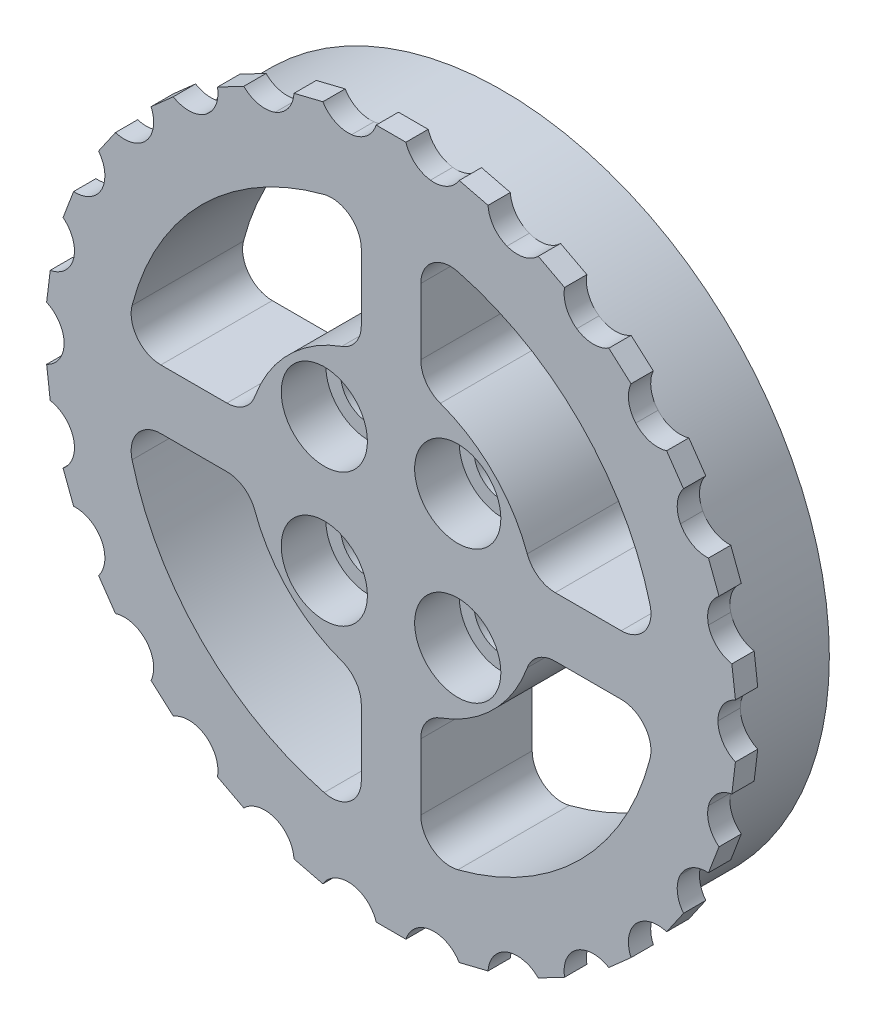
SolidWorks part; units mm, degrees
ref_plane "Front Plane" through (0, 0, 0) normal (0, 0, 1) x (1, 0, 0)
ref_plane "Top Plane" through (0, 0, 0) normal (0, 1, 0) x (1, 0, 0)
ref_plane "Right Plane" through (0, 0, 0) normal (1, 0, 0) x (0, 0, -1)
sketch "Sketch1" plane through (0, 0, 0) normal (0, 0, 1) x (1, 0, 0)
  line L0 (11.0482, 2) -> (15.4919, 2) construction
  line L1 (2, 15.4919) -> (2, 11.0482) construction
  line L2 (-15.4919, 2) -> (-11.0482, 2) construction
  line L3 (-2, 15.4919) -> (-2, 11.0482) construction
  line L4 (11.0482, 2) -> (15.4919, 2)
  line L5 (2, 15.4919) -> (2, 11.0482)
  line L6 (-15.4919, 2) -> (-11.0482, 2)
  line L7 (-2, 15.4919) -> (-2, 11.0482)
  line L8 (2, -11.0482) -> (2, -15.4919) construction
  line L9 (11.0482, -2) -> (15.4919, -2) construction
  line L10 (2, -11.0482) -> (2, -15.4919)
  line L11 (11.0482, -2) -> (15.4919, -2)
  line L12 (-15.4919, -2) -> (-11.0482, -2) construction
  line L13 (-2, -11.0482) -> (-2, -15.4919) construction
  line L14 (-15.4919, -2) -> (-11.0482, -2)
  line L15 (-2, -11.0482) -> (-2, -15.4919)
  circle A0 centre (0, 0) radius 22 construction
  circle A1 centre (0, 0) radius 22
  arc A2 (2, 11.0482) -> (3.3191, 9.1676) centre (4, 11.0482) ccw construction
  arc A3 (9.1676, 3.3191) -> (3.3191, 9.1676) centre (0, 0) ccw construction
  arc A4 (9.1676, 3.3191) -> (11.0482, 2) centre (11.0482, 4) ccw construction
  arc A5 (15.4919, 2) -> (17.4284, 4.5) centre (15.4919, 4) ccw construction
  arc A6 (17.4284, 4.5) -> (4.5, 17.4284) centre (0, 0) ccw construction
  arc A7 (4.5, 17.4284) -> (2, 15.4919) centre (4, 15.4919) ccw construction
  arc A8 (-17.4284, 4.5) -> (-15.4919, 2) centre (-15.4919, 4) ccw construction
  arc A9 (-11.0482, 2) -> (-9.1676, 3.3191) centre (-11.0482, 4) ccw construction
  arc A10 (-3.3191, 9.1676) -> (-9.1676, 3.3191) centre (0, 0) ccw construction
  arc A11 (-3.3191, 9.1676) -> (-2, 11.0482) centre (-4, 11.0482) ccw construction
  arc A12 (-2, 15.4919) -> (-4.5, 17.4284) centre (-4, 15.4919) ccw construction
  arc A13 (-4.5, 17.4284) -> (-17.4284, 4.5) centre (0, 0) ccw construction
  arc A14 (2, 11.0482) -> (3.3191, 9.1676) centre (4, 11.0482) ccw
  arc A15 (9.1676, 3.3191) -> (3.3191, 9.1676) centre (0, 0) ccw
  arc A16 (9.1676, 3.3191) -> (11.0482, 2) centre (11.0482, 4) ccw
  arc A17 (15.4919, 2) -> (17.4284, 4.5) centre (15.4919, 4) ccw
  arc A18 (17.4284, 4.5) -> (4.5, 17.4284) centre (0, 0) ccw
  arc A19 (4.5, 17.4284) -> (2, 15.4919) centre (4, 15.4919) ccw
  arc A20 (-17.4284, 4.5) -> (-15.4919, 2) centre (-15.4919, 4) ccw
  arc A21 (-11.0482, 2) -> (-9.1676, 3.3191) centre (-11.0482, 4) ccw
  arc A22 (-3.3191, 9.1676) -> (-9.1676, 3.3191) centre (0, 0) ccw
  arc A23 (-3.3191, 9.1676) -> (-2, 11.0482) centre (-4, 11.0482) ccw
  arc A24 (-2, 15.4919) -> (-4.5, 17.4284) centre (-4, 15.4919) ccw
  arc A25 (-4.5, 17.4284) -> (-17.4284, 4.5) centre (0, 0) ccw
  arc A26 (2, -15.4919) -> (4.5, -17.4284) centre (4, -15.4919) ccw construction
  arc A27 (3.3191, -9.1676) -> (2, -11.0482) centre (4, -11.0482) ccw construction
  arc A28 (3.3191, -9.1676) -> (9.1676, -3.3191) centre (0, 0) ccw construction
  arc A29 (11.0482, -2) -> (9.1676, -3.3191) centre (11.0482, -4) ccw construction
  arc A30 (17.4284, -4.5) -> (15.4919, -2) centre (15.4919, -4) ccw construction
  arc A31 (4.5, -17.4284) -> (17.4284, -4.5) centre (0, 0) ccw construction
  arc A32 (2, -15.4919) -> (4.5, -17.4284) centre (4, -15.4919) ccw
  arc A33 (3.3191, -9.1676) -> (2, -11.0482) centre (4, -11.0482) ccw
  arc A34 (3.3191, -9.1676) -> (9.1676, -3.3191) centre (0, 0) ccw
  arc A35 (11.0482, -2) -> (9.1676, -3.3191) centre (11.0482, -4) ccw
  arc A36 (17.4284, -4.5) -> (15.4919, -2) centre (15.4919, -4) ccw
  arc A37 (4.5, -17.4284) -> (17.4284, -4.5) centre (0, 0) ccw
  arc A38 (-4.5, -17.4284) -> (-2, -15.4919) centre (-4, -15.4919) ccw construction
  arc A39 (-17.4284, -4.5) -> (-4.5, -17.4284) centre (0, 0) ccw construction
  arc A40 (-15.4919, -2) -> (-17.4284, -4.5) centre (-15.4919, -4) ccw construction
  arc A41 (-9.1676, -3.3191) -> (-11.0482, -2) centre (-11.0482, -4) ccw construction
  arc A42 (-9.1676, -3.3191) -> (-3.3191, -9.1676) centre (0, 0) ccw construction
  arc A43 (-2, -11.0482) -> (-3.3191, -9.1676) centre (-4, -11.0482) ccw construction
  arc A44 (-4.5, -17.4284) -> (-2, -15.4919) centre (-4, -15.4919) ccw
  arc A45 (-17.4284, -4.5) -> (-4.5, -17.4284) centre (0, 0) ccw
  arc A46 (-15.4919, -2) -> (-17.4284, -4.5) centre (-15.4919, -4) ccw
  arc A47 (-9.1676, -3.3191) -> (-11.0482, -2) centre (-11.0482, -4) ccw
  arc A48 (-9.1676, -3.3191) -> (-3.3191, -9.1676) centre (0, 0) ccw
  arc A49 (-2, -11.0482) -> (-3.3191, -9.1676) centre (-4, -11.0482) ccw
extrude "Boss-Extrude1" add sketch "Sketch1" along normal blind 6
sketch "Sketch2" plane through (0, 0, 6) normal (0, 0, 1) x (1, 0, 0)
  line L0 (1, 23.2273) -> (-1, 23.2273) construction
  line L1 (6.5296, 22.313) -> (4.5877, 22.7916) construction
  line L2 (11.6797, 20.102) -> (9.9088, 21.0314) construction
  line L3 (16.151, 16.7227) -> (14.654, 18.049) construction
  line L4 (19.6837, 12.3716) -> (18.5476, 14.0176) construction
  line L5 (22.0725, 7.3015) -> (21.3633, 9.1715) construction
  line L6 (23.1784, 1.807) -> (22.9374, 3.7924) construction
  line L7 (22.9374, -3.7924) -> (23.1784, -1.807) construction
  line L8 (21.3633, -9.1715) -> (22.0725, -7.3015) construction
  line L9 (18.5476, -14.0176) -> (19.6837, -12.3716) construction
  line L10 (14.654, -18.049) -> (16.151, -16.7227) construction
  line L11 (9.9088, -21.0314) -> (11.6797, -20.102) construction
  line L12 (4.5877, -22.7916) -> (6.5296, -22.313) construction
  line L13 (-1, -23.2273) -> (1, -23.2273) construction
  line L14 (-6.5296, -22.313) -> (-4.5877, -22.7916) construction
  line L15 (-11.6797, -20.102) -> (-9.9088, -21.0314) construction
  line L16 (-16.151, -16.7227) -> (-14.654, -18.049) construction
  line L17 (-19.6837, -12.3716) -> (-18.5476, -14.0176) construction
  line L18 (-22.0725, -7.3015) -> (-21.3633, -9.1715) construction
  line L19 (-23.1784, -1.807) -> (-22.9374, -3.7924) construction
  line L20 (-22.9374, 3.7924) -> (-23.1784, 1.807) construction
  line L21 (-21.3633, 9.1715) -> (-22.0725, 7.3015) construction
  line L22 (-4.5877, 22.7916) -> (-6.5296, 22.313) construction
  line L23 (-9.9088, 21.0314) -> (-11.6797, 20.102) construction
  line L24 (-14.654, 18.049) -> (-16.151, 16.7227) construction
  line L25 (-18.5476, 14.0176) -> (-19.6837, 12.3716) construction
  line L26 (-4.5877, 22.7916) -> (-6.5296, 22.313)
  line L27 (-9.9088, 21.0314) -> (-11.6797, 20.102)
  line L28 (-14.654, 18.049) -> (-16.151, 16.7227)
  line L29 (-18.5476, 14.0176) -> (-19.6837, 12.3716)
  line L30 (-21.3633, 9.1715) -> (-22.0725, 7.3015)
  line L31 (-22.9374, 3.7924) -> (-23.1784, 1.807)
  line L32 (-23.1784, -1.807) -> (-22.9374, -3.7924)
  line L33 (-22.0725, -7.3015) -> (-21.3633, -9.1715)
  line L34 (-19.6837, -12.3716) -> (-18.5476, -14.0176)
  line L35 (-16.151, -16.7227) -> (-14.654, -18.049)
  line L36 (-11.6797, -20.102) -> (-9.9088, -21.0314)
  line L37 (-6.5296, -22.313) -> (-4.5877, -22.7916)
  line L38 (-1, -23.2273) -> (1, -23.2273)
  line L39 (4.5877, -22.7916) -> (6.5296, -22.313)
  line L40 (9.9088, -21.0314) -> (11.6797, -20.102)
  line L41 (14.654, -18.049) -> (16.151, -16.7227)
  line L42 (18.5476, -14.0176) -> (19.6837, -12.3716)
  line L43 (21.3633, -9.1715) -> (22.0725, -7.3015)
  line L44 (22.9374, -3.7924) -> (23.1784, -1.807)
  line L45 (23.1784, 1.807) -> (22.9374, 3.7924)
  line L46 (22.0725, 7.3015) -> (21.3633, 9.1715)
  line L47 (19.6837, 12.3716) -> (18.5476, 14.0176)
  line L48 (16.151, 16.7227) -> (14.654, 18.049)
  line L49 (11.6797, 20.102) -> (9.9088, 21.0314)
  line L50 (6.5296, 22.313) -> (4.5877, 22.7916)
  line L51 (1, 23.2273) -> (-1, 23.2273)
  line L54 (-2, 11.0482) -> (-2, 15.4919)
  line L55 (-15.4919, 2) -> (-11.0482, 2)
  line L56 (-2, 11.0482) -> (-2, 15.4919)
  line L57 (-15.4919, 2) -> (-11.0482, 2)
  line L58 (2, 15.4919) -> (2, 11.0482)
  line L59 (11.0482, 2) -> (15.4919, 2)
  line L60 (2, 15.4919) -> (2, 11.0482)
  line L61 (11.0482, 2) -> (15.4919, 2)
  line L62 (2, -11.0482) -> (2, -15.4919)
  line L63 (15.4919, -2) -> (11.0482, -2)
  line L64 (2, -11.0482) -> (2, -15.4919)
  line L65 (15.4919, -2) -> (11.0482, -2)
  line L66 (-11.0482, -2) -> (-15.4919, -2)
  line L67 (-2, -15.4919) -> (-2, -11.0482)
  line L68 (-11.0482, -2) -> (-15.4919, -2)
  line L69 (-2, -15.4919) -> (-2, -11.0482)
  arc A4 (-6.5296, -22.313) -> (-7.8013, -20.5704) centre (-8.5259, -22.4346) ccw construction
  arc A5 (-6.5296, -22.313) -> (-7.8013, -20.5704) centre (-8.5259, -22.4346) ccw
  arc A6 (-23.1784, -1.807) -> (-22.0001, 0) centre (-24, 0.0164) ccw construction
  arc A7 (-17.4284, 4.5) -> (-15.4919, 2) centre (-15.4919, 4) ccw
  arc A8 (-4.5, 17.4284) -> (-17.4284, 4.5) centre (0, 0) ccw
  arc A9 (-2, 15.4919) -> (-4.5, 17.4284) centre (-4, 15.4919) ccw
  arc A10 (-3.3191, 9.1676) -> (-2, 11.0482) centre (-4, 11.0482) ccw
  arc A11 (-3.3191, 9.1676) -> (-9.1676, 3.3191) centre (0, 0) ccw
  arc A12 (-11.0482, 2) -> (-9.1676, 3.3191) centre (-11.0482, 4) ccw
  arc A13 (-17.4284, 4.5) -> (-15.4919, 2) centre (-15.4919, 4) ccw
  arc A14 (-4.5, 17.4284) -> (-17.4284, 4.5) centre (0, 0) ccw
  arc A15 (-2, 15.4919) -> (-4.5, 17.4284) centre (-4, 15.4919) ccw
  arc A16 (-3.3191, 9.1676) -> (-2, 11.0482) centre (-4, 11.0482) ccw
  arc A17 (-3.3191, 9.1676) -> (-9.1676, 3.3191) centre (0, 0) ccw
  arc A18 (-11.0482, 2) -> (-9.1676, 3.3191) centre (-11.0482, 4) ccw
  arc A19 (-23.1784, -1.807) -> (-22.0001, 0) centre (-24, 0.0164) ccw
  arc A20 (9.1676, 3.3191) -> (3.3191, 9.1676) centre (0, 0) ccw
  arc A21 (2, 11.0482) -> (3.3191, 9.1676) centre (4, 11.0482) ccw
  arc A22 (4.5, 17.4284) -> (2, 15.4919) centre (4, 15.4919) ccw
  arc A23 (17.4284, 4.5) -> (4.5, 17.4284) centre (0, 0) ccw
  arc A24 (15.4919, 2) -> (17.4284, 4.5) centre (15.4919, 4) ccw
  arc A25 (9.1676, 3.3191) -> (11.0482, 2) centre (11.0482, 4) ccw
  arc A26 (9.1676, 3.3191) -> (3.3191, 9.1676) centre (0, 0) ccw
  arc A27 (2, 11.0482) -> (3.3191, 9.1676) centre (4, 11.0482) ccw
  arc A28 (4.5877, -22.7916) -> (2.6518, -21.8397) centre (2.8766, -23.827) ccw construction
  arc A29 (-4.5877, 22.7916) -> (-2.6518, 21.8397) centre (-2.8766, 23.827) ccw construction
  arc A30 (-2.6518, 21.8397) -> (-1, 23.2273) centre (-2.9092, 23.823) ccw construction
  arc A31 (7.8013, 20.5704) -> (9.9088, 21.0314) centre (8.4951, 22.4462) ccw construction
  arc A32 (1, 23.2273) -> (2.6518, 21.8397) centre (2.9092, 23.823) ccw construction
  arc A33 (2.6518, 21.8397) -> (4.5877, 22.7916) centre (2.8766, 23.827) ccw construction
  arc A34 (6.5296, 22.313) -> (7.8013, 20.5704) centre (8.5259, 22.4346) ccw construction
  arc A36 (11.6797, 20.102) -> (12.4975, 18.1057) centre (13.6471, 19.7423) ccw construction
  arc A37 (12.4975, 18.1057) -> (14.654, 18.049) centre (13.62, 19.761) ccw construction
  arc A38 (16.151, 16.7227) -> (16.4673, 14.5887) centre (17.9752, 15.9026) ccw construction
  arc A39 (16.4673, 14.5887) -> (18.5476, 14.0176) centre (17.9533, 15.9272) ccw construction
  arc A40 (19.6837, 12.3716) -> (19.4801, 10.2239) centre (21.2586, 11.1388) ccw construction
  arc A41 (19.4801, 10.2239) -> (21.3633, 9.1715) centre (21.2433, 11.1679) ccw construction
  arc A42 (22.0725, 7.3015) -> (21.3608, 5.265) centre (23.3065, 5.7276) ccw construction
  arc A43 (21.3608, 5.265) -> (22.9374, 3.7924) centre (23.2987, 5.7595) ccw construction
  arc A44 (23.1784, 1.807) -> (22.0001, 0) centre (24, -0.0164) ccw construction
  arc A45 (22.0001, 0) -> (23.1784, -1.807) centre (24, 0.0164) ccw construction
  arc A46 (22.9374, -3.7924) -> (21.3608, -5.265) centre (23.2987, -5.7595) ccw construction
  arc A47 (21.3608, -5.265) -> (22.0725, -7.3015) centre (23.3065, -5.7276) ccw construction
  arc A48 (21.3633, -9.1715) -> (19.4801, -10.2239) centre (21.2433, -11.1679) ccw construction
  arc A49 (19.4801, -10.2239) -> (19.6837, -12.3716) centre (21.2586, -11.1388) ccw construction
  arc A50 (18.5476, -14.0176) -> (16.4673, -14.5887) centre (17.9533, -15.9272) ccw construction
  arc A51 (16.4673, -14.5887) -> (16.151, -16.7227) centre (17.9752, -15.9026) ccw construction
  arc A52 (14.654, -18.049) -> (12.4975, -18.1057) centre (13.62, -19.761) ccw construction
  arc A53 (12.4975, -18.1057) -> (11.6797, -20.102) centre (13.6471, -19.7423) ccw construction
  arc A54 (9.9088, -21.0314) -> (7.8013, -20.5704) centre (8.4951, -22.4462) ccw construction
  arc A55 (7.8013, -20.5704) -> (6.5296, -22.313) centre (8.5259, -22.4346) ccw construction
  arc A56 (2.6518, -21.8397) -> (1, -23.2273) centre (2.9092, -23.823) ccw construction
  arc A57 (-1, -23.2273) -> (-2.6518, -21.8397) centre (-2.9092, -23.823) ccw construction
  arc A58 (-2.6518, -21.8397) -> (-4.5877, -22.7916) centre (-2.8766, -23.827) ccw construction
  arc A59 (-7.8013, -20.5704) -> (-9.9088, -21.0314) centre (-8.4951, -22.4462) ccw construction
  arc A60 (-11.6797, -20.102) -> (-12.4975, -18.1057) centre (-13.6471, -19.7423) ccw construction
  arc A61 (-12.4975, -18.1057) -> (-14.654, -18.049) centre (-13.62, -19.761) ccw construction
  arc A62 (-16.151, -16.7227) -> (-16.4673, -14.5887) centre (-17.9752, -15.9026) ccw construction
  arc A63 (-16.4673, -14.5887) -> (-18.5476, -14.0176) centre (-17.9533, -15.9272) ccw construction
  arc A64 (-19.6837, -12.3716) -> (-19.4801, -10.2239) centre (-21.2586, -11.1388) ccw construction
  arc A65 (-19.4801, -10.2239) -> (-21.3633, -9.1715) centre (-21.2433, -11.1679) ccw construction
  arc A66 (-22.0725, -7.3015) -> (-21.3608, -5.265) centre (-23.3065, -5.7276) ccw construction
  arc A67 (-21.3608, -5.265) -> (-22.9374, -3.7924) centre (-23.2987, -5.7595) ccw construction
  arc A68 (-21.3633, 9.1715) -> (-19.4801, 10.2239) centre (-21.2433, 11.1679) ccw construction
  arc A69 (-22.0001, 0) -> (-23.1784, 1.807) centre (-24, -0.0164) ccw construction
  arc A70 (-22.9374, 3.7924) -> (-21.3608, 5.265) centre (-23.2987, 5.7595) ccw construction
  arc A71 (-21.3608, 5.265) -> (-22.0725, 7.3015) centre (-23.3065, 5.7276) ccw construction
  arc A72 (-7.8013, 20.5704) -> (-6.5296, 22.313) centre (-8.5259, 22.4346) ccw construction
  arc A73 (-9.9088, 21.0314) -> (-7.8013, 20.5704) centre (-8.4951, 22.4462) ccw construction
  arc A74 (-12.4975, 18.1057) -> (-11.6797, 20.102) centre (-13.6471, 19.7423) ccw construction
  arc A75 (-14.654, 18.049) -> (-12.4975, 18.1057) centre (-13.62, 19.761) ccw construction
  arc A76 (-16.4673, 14.5887) -> (-16.151, 16.7227) centre (-17.9752, 15.9026) ccw construction
  arc A77 (-18.5476, 14.0176) -> (-16.4673, 14.5887) centre (-17.9533, 15.9272) ccw construction
  arc A78 (-19.4801, 10.2239) -> (-19.6837, 12.3716) centre (-21.2586, 11.1388) ccw construction
  arc A79 (-4.5877, 22.7916) -> (-2.6518, 21.8397) centre (-2.8766, 23.827) ccw
  arc A80 (-7.8013, 20.5704) -> (-6.5296, 22.313) centre (-8.5259, 22.4346) ccw
  arc A81 (-9.9088, 21.0314) -> (-7.8013, 20.5704) centre (-8.4951, 22.4462) ccw
  arc A82 (-12.4975, 18.1057) -> (-11.6797, 20.102) centre (-13.6471, 19.7423) ccw
  arc A83 (-14.654, 18.049) -> (-12.4975, 18.1057) centre (-13.62, 19.761) ccw
  arc A84 (-16.4673, 14.5887) -> (-16.151, 16.7227) centre (-17.9752, 15.9026) ccw
  arc A85 (-18.5476, 14.0176) -> (-16.4673, 14.5887) centre (-17.9533, 15.9272) ccw
  arc A86 (-19.4801, 10.2239) -> (-19.6837, 12.3716) centre (-21.2586, 11.1388) ccw
  arc A87 (-21.3633, 9.1715) -> (-19.4801, 10.2239) centre (-21.2433, 11.1679) ccw
  arc A88 (-21.3608, 5.265) -> (-22.0725, 7.3015) centre (-23.3065, 5.7276) ccw
  arc A89 (-22.9374, 3.7924) -> (-21.3608, 5.265) centre (-23.2987, 5.7595) ccw
  arc A90 (-22.0001, 0) -> (-23.1784, 1.807) centre (-24, -0.0164) ccw
  arc A91 (-21.3608, -5.265) -> (-22.9374, -3.7924) centre (-23.2987, -5.7595) ccw
  arc A92 (-22.0725, -7.3015) -> (-21.3608, -5.265) centre (-23.3065, -5.7276) ccw
  arc A93 (-19.4801, -10.2239) -> (-21.3633, -9.1715) centre (-21.2433, -11.1679) ccw
  arc A94 (-19.6837, -12.3716) -> (-19.4801, -10.2239) centre (-21.2586, -11.1388) ccw
  arc A95 (-16.4673, -14.5887) -> (-18.5476, -14.0176) centre (-17.9533, -15.9272) ccw
  arc A96 (-16.151, -16.7227) -> (-16.4673, -14.5887) centre (-17.9752, -15.9026) ccw
  arc A97 (-12.4975, -18.1057) -> (-14.654, -18.049) centre (-13.62, -19.761) ccw
  arc A98 (-11.6797, -20.102) -> (-12.4975, -18.1057) centre (-13.6471, -19.7423) ccw
  arc A99 (-7.8013, -20.5704) -> (-9.9088, -21.0314) centre (-8.4951, -22.4462) ccw
  arc A100 (-2.6518, -21.8397) -> (-4.5877, -22.7916) centre (-2.8766, -23.827) ccw
  arc A101 (-1, -23.2273) -> (-2.6518, -21.8397) centre (-2.9092, -23.823) ccw
  arc A102 (2.6518, -21.8397) -> (1, -23.2273) centre (2.9092, -23.823) ccw
  arc A103 (4.5877, -22.7916) -> (2.6518, -21.8397) centre (2.8766, -23.827) ccw
  arc A104 (7.8013, -20.5704) -> (6.5296, -22.313) centre (8.5259, -22.4346) ccw
  arc A105 (9.9088, -21.0314) -> (7.8013, -20.5704) centre (8.4951, -22.4462) ccw
  arc A106 (12.4975, -18.1057) -> (11.6797, -20.102) centre (13.6471, -19.7423) ccw
  arc A107 (14.654, -18.049) -> (12.4975, -18.1057) centre (13.62, -19.761) ccw
  arc A108 (16.4673, -14.5887) -> (16.151, -16.7227) centre (17.9752, -15.9026) ccw
  arc A109 (18.5476, -14.0176) -> (16.4673, -14.5887) centre (17.9533, -15.9272) ccw
  arc A110 (19.4801, -10.2239) -> (19.6837, -12.3716) centre (21.2586, -11.1388) ccw
  arc A111 (21.3633, -9.1715) -> (19.4801, -10.2239) centre (21.2433, -11.1679) ccw
  arc A112 (21.3608, -5.265) -> (22.0725, -7.3015) centre (23.3065, -5.7276) ccw
  arc A113 (22.9374, -3.7924) -> (21.3608, -5.265) centre (23.2987, -5.7595) ccw
  arc A114 (22.0001, 0) -> (23.1784, -1.807) centre (24, 0.0164) ccw
  arc A115 (23.1784, 1.807) -> (22.0001, 0) centre (24, -0.0164) ccw
  arc A116 (21.3608, 5.265) -> (22.9374, 3.7924) centre (23.2987, 5.7595) ccw
  arc A117 (22.0725, 7.3015) -> (21.3608, 5.265) centre (23.3065, 5.7276) ccw
  arc A118 (19.4801, 10.2239) -> (21.3633, 9.1715) centre (21.2433, 11.1679) ccw
  arc A119 (19.6837, 12.3716) -> (19.4801, 10.2239) centre (21.2586, 11.1388) ccw
  arc A120 (16.4673, 14.5887) -> (18.5476, 14.0176) centre (17.9533, 15.9272) ccw
  arc A121 (16.151, 16.7227) -> (16.4673, 14.5887) centre (17.9752, 15.9026) ccw
  arc A122 (12.4975, 18.1057) -> (14.654, 18.049) centre (13.62, 19.761) ccw
  arc A123 (11.6797, 20.102) -> (12.4975, 18.1057) centre (13.6471, 19.7423) ccw
  arc A124 (7.8013, 20.5704) -> (9.9088, 21.0314) centre (8.4951, 22.4462) ccw
  arc A125 (6.5296, 22.313) -> (7.8013, 20.5704) centre (8.5259, 22.4346) ccw
  arc A126 (2.6518, 21.8397) -> (4.5877, 22.7916) centre (2.8766, 23.827) ccw
  arc A127 (1, 23.2273) -> (2.6518, 21.8397) centre (2.9092, 23.823) ccw
  arc A128 (-2.6518, 21.8397) -> (-1, 23.2273) centre (-2.9092, 23.823) ccw
  arc A129 (4.5, 17.4284) -> (2, 15.4919) centre (4, 15.4919) ccw
  arc A130 (17.4284, 4.5) -> (4.5, 17.4284) centre (0, 0) ccw
  arc A131 (15.4919, 2) -> (17.4284, 4.5) centre (15.4919, 4) ccw
  arc A132 (9.1676, 3.3191) -> (11.0482, 2) centre (11.0482, 4) ccw
  arc A134 (4.5, -17.4284) -> (17.4284, -4.5) centre (0, 0) ccw
  arc A135 (2, -15.4919) -> (4.5, -17.4284) centre (4, -15.4919) ccw
  arc A136 (3.3191, -9.1676) -> (2, -11.0482) centre (4, -11.0482) ccw
  arc A137 (3.3191, -9.1676) -> (9.1676, -3.3191) centre (0, 0) ccw
  arc A138 (11.0482, -2) -> (9.1676, -3.3191) centre (11.0482, -4) ccw
  arc A139 (17.4284, -4.5) -> (15.4919, -2) centre (15.4919, -4) ccw
  arc A140 (4.5, -17.4284) -> (17.4284, -4.5) centre (0, 0) ccw
  arc A141 (2, -15.4919) -> (4.5, -17.4284) centre (4, -15.4919) ccw
  arc A142 (3.3191, -9.1676) -> (2, -11.0482) centre (4, -11.0482) ccw
  arc A143 (3.3191, -9.1676) -> (9.1676, -3.3191) centre (0, 0) ccw
  arc A144 (11.0482, -2) -> (9.1676, -3.3191) centre (11.0482, -4) ccw
  arc A145 (17.4284, -4.5) -> (15.4919, -2) centre (15.4919, -4) ccw
  arc A147 (-4.5, -17.4284) -> (-2, -15.4919) centre (-4, -15.4919) ccw
  arc A148 (-17.4284, -4.5) -> (-4.5, -17.4284) centre (0, 0) ccw
  arc A149 (-15.4919, -2) -> (-17.4284, -4.5) centre (-15.4919, -4) ccw
  arc A150 (-9.1676, -3.3191) -> (-11.0482, -2) centre (-11.0482, -4) ccw
  arc A151 (-9.1676, -3.3191) -> (-3.3191, -9.1676) centre (0, 0) ccw
  arc A152 (-2, -11.0482) -> (-3.3191, -9.1676) centre (-4, -11.0482) ccw
  arc A153 (-4.5, -17.4284) -> (-2, -15.4919) centre (-4, -15.4919) ccw
  arc A154 (-17.4284, -4.5) -> (-4.5, -17.4284) centre (0, 0) ccw
  arc A155 (-15.4919, -2) -> (-17.4284, -4.5) centre (-15.4919, -4) ccw
  arc A156 (-9.1676, -3.3191) -> (-11.0482, -2) centre (-11.0482, -4) ccw
  arc A157 (-9.1676, -3.3191) -> (-3.3191, -9.1676) centre (0, 0) ccw
  arc A158 (-2, -11.0482) -> (-3.3191, -9.1676) centre (-4, -11.0482) ccw
  dimension "D1" = 0
  dimension "D2" = 0
  dimension "D3" = 0
  dimension "D4" = 0
extrude "Boss-Extrude2" add sketch "Sketch2" along normal blind 1.5
sketch "Sketch3" plane through (0, 0, 0) normal (0, 0, -1) x (-1, 0, 0)
  circle A0 centre (0, 8) radius 1.5
  circle A1 centre (0, 8) radius 1.5 construction
  circle A2 centre (8, 0) radius 1.5
  circle A3 centre (8, 0) radius 1.5 construction
  circle A4 centre (0, -8) radius 1.5
  circle A5 centre (0, -8) radius 1.5 construction
  circle A6 centre (-8, 0) radius 1.5
  circle A7 centre (-8, 0) radius 1.5 construction
  circle A8 centre (8, 0) radius 1.375
  circle A9 centre (0, -8) radius 1.375
  circle A10 centre (0, 8) radius 1.375
  circle A11 centre (-8, 0) radius 1.375
  dimension "D1" = 0.125
extrude "Boss-Extrude3" add sketch "Sketch3" along normal blind 2.5 contours A8 | A10 | A11 | A9 region at (-8, 0, 0) region at (0, -8, 0) region at (0, 8, 0) region at (8, 0, 0)
sketch "Sketch4" [suppressed] plane through (0, 0, 7.5) normal (0, 0, 1) x (1, 0, 0)
  circle A0 centre (0, 0) radius 2.15
  dimension "D1" = 4.3
extrude "Cut-Extrude1" [suppressed] cut sketch "Sketch4" against normal up to next
sketch "Sketch5" [suppressed] plane through (0, 0, 7.5) normal (0, 0, 1) x (1, 0, 0)
  circle A0 centre (0, 0) radius 5.25
  dimension "D1" = 10.5
extrude "Cut-Extrude2" [suppressed] cut sketch "Sketch5" against normal offset from surface (5.5 mm away) 2 up to face at (1.375, -8, 0)
sketch "Sketch6" plane through (0, 0, 7.5) normal (0, 0, 1) x (1, 0, 0)
  line L0 (0, 0) -> (6.8943, 6.8943) construction
  line L1 (0, 6.35) -> (0, -6.35) construction
  line L2 (-6.35, 0) -> (6.35, 0) construction
  circle A0 centre (0, 0) radius 6.35
  arc A1 (9.1676, 3.3191) -> (3.3191, 9.1676) centre (0, 0) ccw construction
  circle A2 centre (4.4901, 4.4901) radius 1.9
  circle A3 centre (-4.4901, 4.4901) radius 1.9
  circle A4 centre (4.4901, -4.4901) radius 1.9
  circle A5 centre (-4.4901, -4.4901) radius 1.9
  dimension "D1" = 12.7
  dimension "D2" = 3.8
extrude "Cut-Extrude3" cut sketch "Sketch6" against normal up to next contours A3 A0 | A3 A0 | A0 A2 | A0 A2 | A4 A0 | A4 A0 | A0 A5 | A0 A5 region at (3.8853, 3.8853, 7.5) region at (5.0226, 5.0226, 7.5) region at (5.0226, -5.0226, 7.5) region at (3.8853, -3.8853, 7.5) region at (-3.8853, 3.8853, 7.5) region at (-5.0226, 5.0226, 7.5) region at (-5.0226, -5.0226, 7.5) region at (-3.8853, -3.8853, 7.5)
sketch "Sketch7" plane through (0, 0, 7.5) normal (0, 0, 1) x (1, 0, 0)
  circle A0 centre (-4.4901, 4.4901) radius 2.9
  circle A1 centre (4.4901, 4.4901) radius 2.9
  circle A2 centre (4.4901, -4.4901) radius 2.9
  circle A3 centre (-4.4901, -4.4901) radius 2.9
  dimension "D1" = 5.8
extrude "Cut-Extrude4" cut sketch "Sketch7" against normal blind 3
